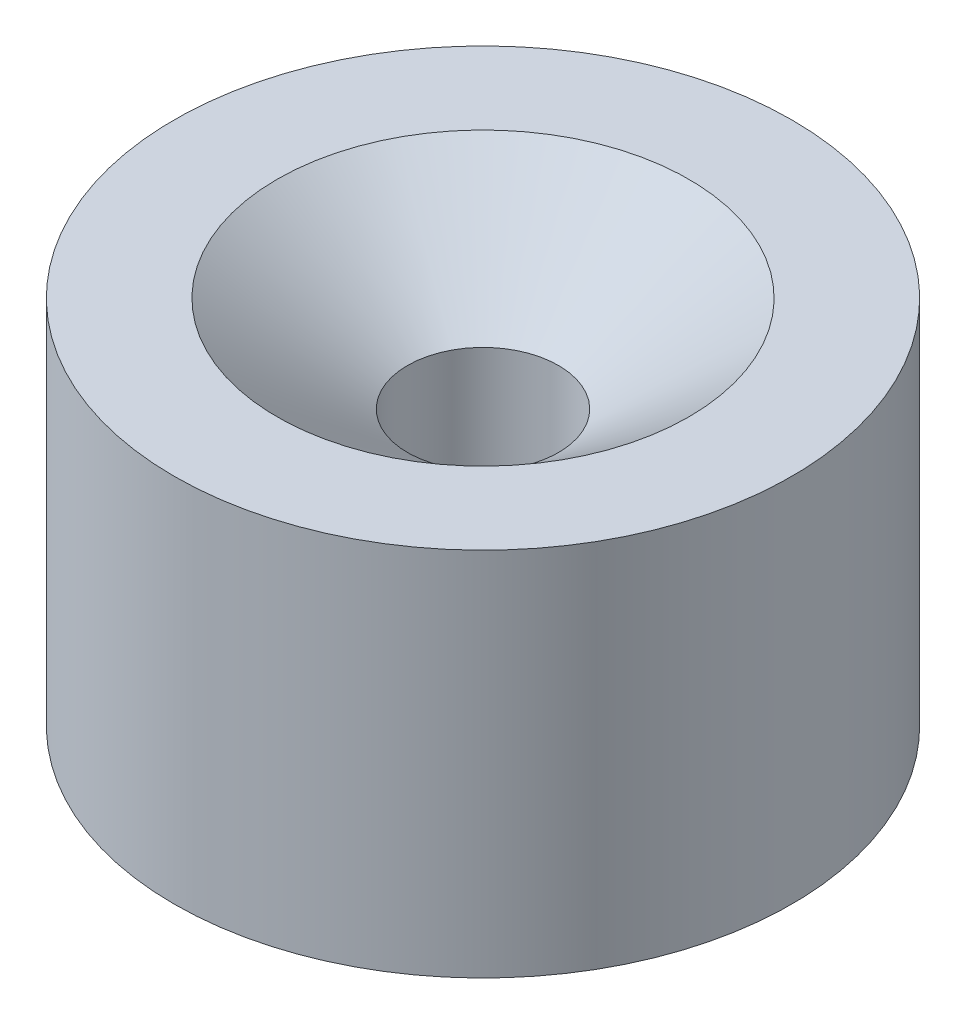
SolidWorks part; units mm, degrees
material "POLYURETHANE (11671)"
ref_plane "Front Plane" through (0, 0, 0) normal (0, 0, 1) x (1, 0, 0)
ref_plane "Top Plane" through (0, 0, 0) normal (0, 1, 0) x (1, 0, 0)
ref_plane "Right Plane" through (0, 0, 0) normal (1, 0, 0) x (0, 0, -1)
sketch "Sketch1" plane through (0, 0, 0) normal (0, 1, 0) x (1, 0, 0)
  circle A0 centre (0, 0) radius 45
  dimension "D1" = 90
extrude "Boss-Extrude1" add sketch "Sketch1" along normal blind 54
sketch "Sketch8" plane through (0, 0, 0) normal (0, 0, 1) x (1, 0, 0)
  line L0 (0, 0) -> (0, 54) construction
  line L1 (0, 54) -> (-30, 54)
  line L6 (45, 54) -> (-45, 54) construction
  line L7 (0, 54) -> (0, 40)
  line L8 (0, 40) -> (-11, 40)
  line L9 (-30, 54) -> (-11, 40)
  line L10 (0, 27) -> (-45, 27) construction
  line L11 (-45, 54) -> (-45, 0) construction
  line L12 (0, 0) -> (-30, 0)
  line L13 (0, 14) -> (-11, 14)
  line L14 (0, 0) -> (0, 14)
  line L15 (-30, 0) -> (-11, 14)
  dimension "D1" = 14
  dimension "D2" = 11
  dimension "D3" = 30
revolve "Cut-Revolve3" cut sketch "Sketch8" angle 360 about L0
sketch "Sketch9" plane through (0, 40, 0) normal (0, 1, 0) x (1, 0, 0)
  circle A0 centre (0, 0) radius 11
extrude "Cut-Extrude1" cut sketch "Sketch9" against normal through all
